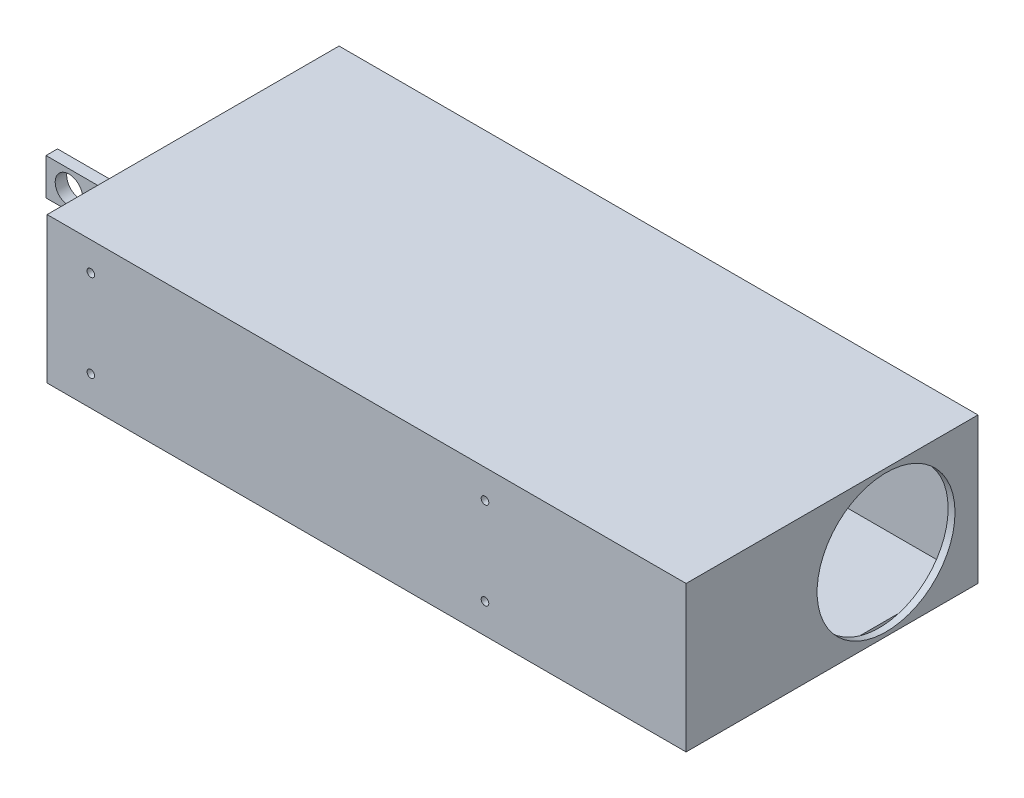
SolidWorks part; units mm, degrees
material "6061-T6 (SS)"
ref_plane "Front Plane" through (0, 0, 0) normal (0, 0, 1) x (1, 0, 0)
ref_plane "Top Plane" through (0, 0, 0) normal (0, 1, 0) x (1, 0, 0)
ref_plane "Right Plane" through (0, 0, 0) normal (1, 0, 0) x (0, 0, -1)
sketch "Sketch1" plane through (0, 0, 0) normal (0, 1, 0) x (1, 0, 0)
  line L1 (139, 63.5) -> (-139, 63.5)
  line L2 (139, 63.5) -> (139, -63.5)
  line L3 (139, -63.5) -> (-139, -63.5)
  line L4 (-139, 63.5) -> (-139, -63.5)
  line L5 (139, 63.5) -> (-139, -63.5) construction
  line L6 (139, -63.5) -> (-139, 63.5) construction
  point P0 (0, 0)
  dimension "D1" = 278
  dimension "D2" = 127
extrude "Boss-Extrude1" add sketch "Sketch1" along normal blind 63.5
sketch "Sketch7" plane through (139, 0, 0) normal (1, 0, 0) x (0, 0, -1)
  line L0 (23.5, 63.5) -> (23.5, 31.75) construction
  line L1 (-63.5, 63.5) -> (63.5, 63.5) construction
  line L2 (23.5, 31.75) -> (23.5, 0) construction
  line L3 (-63.5, 0) -> (63.5, 0) construction
  line L4 (63.5, 63.5) -> (63.5, 0) construction
  circle A0 centre (23.5, 31.75) radius 30
  dimension "D1" = 60
  dimension "D2" = 40
extrude "Cut-Extrude1" cut sketch "Sketch7" against normal blind 3
shell "Shell1" thickness 3 removed face at (136, 31.75, -53.5)
hole_wizard "M4x0.7 Tapped Hole1" positions "Sketch2" profile "Sketch3" tap size "M4x0.7" standard "ANSI Metric"
sketch "Sketch2" plane through (0, 0, 0) normal (0, -1, 0) x (-1, 0, 0)
  line L1 (-51.5, 51.25) -> (120, 51.25)
  line L2 (-51.5, 51.25) -> (-51.5, -50.25)
  line L3 (-51.5, -50.25) -> (120, -50.25)
  line L4 (120, 51.25) -> (120, -50.25)
  line L5 (-51.5, 51.25) -> (120, -50.25) construction
  line L6 (-51.5, -50.25) -> (120, 51.25) construction
  line L7 (139, 63.5) -> (139, -63.5) construction
  line L10 (-139, 63.5) -> (139, 63.5) construction
  point P2 (120, -50.25)
  point P89 (-51.5, 51.25)
  point P90 (-51.5, -50.25)
  point P91 (120, 51.25)
  dimension "D1" = 101.5
  dimension "D2" = 171.5
  dimension "D3" = 19
  dimension "D4" = 12.25
sketch "Sketch3" plane through (-120, 0, 50.25) normal (1, 0, 0) x (0, 0, -1)
  line L0 (0, 0) -> (0, 11.0914)
  line L1 (0, 11.0914) -> (1.65, 10.1)
  line L2 (1.65, 10.1) -> (1.65, 0)
  line L5 (1.65, 0) -> (0, 0)
  line L10 (0, 11.0914) -> (-1.65, 10.1) construction
  line L11 (0, -6.35) -> (0, 107.95) construction
  dimension "Tap Drill Dia." = 3.3
  dimension "Tap Drill Depth" = 10.1
  dimension "Drill Angle" = 118
cosmetic thread "Hole Thread1" parameters "D1"=8, "D2"=4
cosmetic thread "Hole Thread2" parameters "D1"=8, "D2"=4
cosmetic thread "Hole Thread3" parameters "D1"=8, "D2"=4
cosmetic thread "Hole Thread4" parameters "D1"=8, "D2"=4
hole_wizard "M4x0.7 Tapped Hole2" positions "Sketch4" profile "Sketch5" tap size "M4x0.7" standard "ANSI Metric"
sketch "Sketch4" plane through (0, 0, -63.5) normal (0, 0, -1) x (-1, 0, 0)
  line L1 (-51.5, 51) -> (120, 51)
  line L2 (-51.5, 51) -> (-51.5, 13)
  line L3 (-51.5, 13) -> (120, 13)
  line L4 (120, 51) -> (120, 13)
  line L5 (-51.5, 51) -> (120, 13) construction
  line L6 (-51.5, 13) -> (120, 51) construction
  line L8 (-139, 63.5) -> (139, 63.5) construction
  line L15 (139, 63.5) -> (139, 0) construction
  point P2 (120, 13)
  point P101 (-51.5, 51)
  point P102 (-51.5, 13)
  point P103 (120, 51)
  dimension "D1" = 171.5
  dimension "D2" = 38
  dimension "D3" = 19
  dimension "D4" = 12.5
sketch "Sketch5" plane through (-120, 13, -63.5) normal (1, 0, 0) x (0, 1, 0)
  line L0 (0, 0) -> (0, 11.0914)
  line L1 (0, 11.0914) -> (1.65, 10.1)
  line L2 (1.65, 10.1) -> (1.65, 0)
  line L5 (1.65, 0) -> (0, 0)
  line L10 (0, 11.0914) -> (-1.65, 10.1) construction
  line L11 (0, -6.35) -> (0, 107.95) construction
  dimension "Tap Drill Dia." = 3.3
  dimension "Tap Drill Depth" = 10.1
  dimension "Drill Angle" = 118
cosmetic thread "Hole Thread5" parameters "D1"=8, "D2"=4
cosmetic thread "Hole Thread6" parameters "D1"=8, "D2"=4
cosmetic thread "Hole Thread7" parameters "D1"=8, "D2"=4
cosmetic thread "Hole Thread8" parameters "D1"=8, "D2"=4
mirror "Mirror1" about plane through (0, 0, 0) normal (0, 0, 1) of "M4x0.7 Tapped Hole2"
sketch "Sketch6" plane through (-139, 0, 0) normal (-1, 0, 0) x (0, 0, 1)
  line L0 (-63.5, 0) -> (63.5, 0) construction
  line L1 (-5, 5) -> (0, 5)
  line L2 (-5, 5) -> (-5, 21)
  line L3 (-5, 21) -> (0, 21)
  line L4 (0, 5) -> (0, 21)
  line L5 (-5, 5) -> (0, 21) construction
  line L6 (-5, 21) -> (0, 5) construction
  line L7 (20, 31) -> (25, 31)
  line L8 (20, 31) -> (20, 47)
  line L9 (20, 47) -> (25, 47)
  line L10 (25, 31) -> (25, 47)
  line L11 (20, 31) -> (25, 47) construction
  line L12 (20, 47) -> (25, 31) construction
  point P0 (-2.5, 13)
  point P5 (22.5, 39)
  point P10 (0, 0)
  point P14 (0, 21.5279)
  point P17 (0, 0)
  dimension "D1" = 16
  dimension "D2" = 5
  dimension "D3" = 5
  dimension "D4" = 10
  dimension "D5" = 20
extrude "Boss-Extrude2" add sketch "Sketch6" along normal blind 39
sketch "Sketch8" plane through (0, 0, -5) normal (0, 0, -1) x (-1, 0, 0)
  line L0 (178, 21) -> (178, 5) construction
  line L1 (178, 13) -> (168, 13) construction
  line L2 (168, 39) -> (178, 39) construction
  line L3 (178, 47) -> (178, 31) construction
  circle A0 centre (168, 13) radius 6
  circle A1 centre (168, 39) radius 6
  point P7 (0, 0)
  dimension "D1" = 12
  dimension "D2" = 10
extrude "Cut-Extrude2" cut sketch "Sketch8" against normal through all
sketch "Sketch9" plane through (-139, 0, 0) normal (-1, 0, 0) x (0, 0, 1)
  line L0 (-63.5, 63.5) -> (-63.5, 0) construction
  line L1 (-55.5, 3) -> (-47.5, 3)
  line L2 (-55.5, 3) -> (-55.5, 8)
  line L3 (-55.5, 8) -> (-47.5, 8)
  line L4 (-47.5, 3) -> (-47.5, 8)
  line L5 (-63.5, 0) -> (63.5, 0) construction
  line L6 (-45.2, 3) -> (-37.2, 3)
  line L7 (-37.2, 3) -> (-37.2, 8)
  line L8 (-45.2, 8) -> (-37.2, 8)
  line L9 (-45.2, 3) -> (-45.2, 8)
  line L10 (-34.9, 3) -> (-26.9, 3)
  line L11 (-26.9, 3) -> (-26.9, 8)
  line L12 (-34.9, 8) -> (-26.9, 8)
  line L13 (-34.9, 3) -> (-34.9, 8)
  line L14 (-24.6, 3) -> (-16.6, 3)
  line L15 (-16.6, 3) -> (-16.6, 8)
  line L16 (-24.6, 8) -> (-16.6, 8)
  line L17 (-24.6, 3) -> (-24.6, 8)
  line L18 (-14.3, 3) -> (-6.3, 3) [skipped]
  line L19 (-6.3, 3) -> (-6.3, 8) [skipped]
  line L20 (-14.3, 8) -> (-6.3, 8) [skipped]
  line L21 (-14.3, 3) -> (-14.3, 8) [skipped]
  line L22 (-4, 3) -> (4, 3) [skipped]
  line L23 (4, 3) -> (4, 8) [skipped]
  line L24 (-4, 8) -> (4, 8) [skipped]
  line L25 (-4, 3) -> (-4, 8) [skipped]
  line L26 (6.3, 3) -> (14.3, 3)
  line L27 (14.3, 3) -> (14.3, 8)
  line L28 (6.3, 8) -> (14.3, 8)
  line L29 (6.3, 3) -> (6.3, 8)
  line L30 (16.6, 3) -> (24.6, 3)
  line L31 (24.6, 3) -> (24.6, 8)
  line L32 (16.6, 8) -> (24.6, 8)
  line L33 (16.6, 3) -> (16.6, 8)
  line L34 (26.9, 3) -> (34.9, 3)
  line L35 (34.9, 3) -> (34.9, 8)
  line L36 (26.9, 8) -> (34.9, 8)
  line L37 (26.9, 3) -> (26.9, 8)
  line L38 (37.2, 3) -> (45.2, 3)
  line L39 (45.2, 3) -> (45.2, 8)
  line L40 (37.2, 8) -> (45.2, 8)
  line L41 (37.2, 3) -> (37.2, 8)
  line L42 (47.5, 3) -> (55.5, 3)
  line L43 (55.5, 3) -> (55.5, 8)
  line L44 (47.5, 8) -> (55.5, 8)
  line L45 (47.5, 3) -> (47.5, 8)
  line L46 (-50.35, 15.3) -> (-42.35, 15.3)
  line L47 (-60.65, 15.3) -> (-52.65, 15.3)
  line L48 (-60.65, 15.3) -> (-60.65, 10.3)
  line L49 (-60.65, 10.3) -> (-52.65, 10.3)
  line L50 (-52.65, 15.3) -> (-52.65, 10.3)
  line L51 (-50.35, 10.3) -> (-42.35, 10.3)
  line L52 (-42.35, 15.3) -> (-42.35, 10.3)
  line L53 (-50.35, 15.3) -> (-50.35, 10.3)
  line L54 (-40.05, 15.3) -> (-32.05, 15.3)
  line L55 (-40.05, 10.3) -> (-32.05, 10.3)
  line L56 (-32.05, 15.3) -> (-32.05, 10.3)
  line L57 (-40.05, 15.3) -> (-40.05, 10.3)
  line L58 (-29.75, 15.3) -> (-21.75, 15.3)
  line L59 (-29.75, 10.3) -> (-21.75, 10.3)
  line L60 (-21.75, 15.3) -> (-21.75, 10.3)
  line L61 (-29.75, 15.3) -> (-29.75, 10.3)
  line L62 (-19.45, 15.3) -> (-11.45, 15.3)
  line L63 (-19.45, 10.3) -> (-11.45, 10.3)
  line L64 (-11.45, 15.3) -> (-11.45, 10.3)
  line L65 (-19.45, 15.3) -> (-19.45, 10.3)
  line L66 (-45.2, 17.6) -> (-37.2, 17.6)
  line L67 (-55.5, 22.6) -> (-47.5, 22.6)
  line L68 (-55.5, 22.6) -> (-55.5, 17.6)
  line L69 (-55.5, 17.6) -> (-47.5, 17.6)
  line L70 (1.15, 15.3) -> (9.15, 15.3)
  line L71 (1.15, 10.3) -> (9.15, 10.3)
  line L72 (9.15, 15.3) -> (9.15, 10.3)
  line L73 (1.15, 15.3) -> (1.15, 10.3)
  line L74 (11.45, 15.3) -> (19.45, 15.3)
  line L75 (11.45, 10.3) -> (19.45, 10.3)
  line L76 (19.45, 15.3) -> (19.45, 10.3)
  line L77 (11.45, 15.3) -> (11.45, 10.3)
  line L78 (21.75, 15.3) -> (29.75, 15.3)
  line L79 (21.75, 10.3) -> (29.75, 10.3)
  line L80 (29.75, 15.3) -> (29.75, 10.3)
  line L81 (21.75, 15.3) -> (21.75, 10.3)
  line L82 (32.05, 15.3) -> (40.05, 15.3)
  line L83 (32.05, 10.3) -> (40.05, 10.3)
  line L84 (40.05, 15.3) -> (40.05, 10.3)
  line L85 (32.05, 15.3) -> (32.05, 10.3)
  line L86 (42.35, 15.3) -> (50.35, 15.3)
  line L87 (42.35, 10.3) -> (50.35, 10.3)
  line L88 (50.35, 15.3) -> (50.35, 10.3)
  line L89 (42.35, 15.3) -> (42.35, 10.3)
  line L90 (52.65, 15.3) -> (60.65, 15.3)
  line L91 (52.65, 10.3) -> (60.65, 10.3)
  line L92 (60.65, 15.3) -> (60.65, 10.3)
  line L93 (52.65, 15.3) -> (52.65, 10.3)
  line L94 (63.5, 63.5) -> (63.5, 0) construction
  line L95 (-9.15, 15.3) -> (-1.15, 15.3) [skipped]
  line L96 (-9.15, 10.3) -> (-1.15, 10.3) [skipped]
  line L97 (-1.15, 15.3) -> (-1.15, 10.3) [skipped]
  line L98 (-9.15, 15.3) -> (-9.15, 10.3) [skipped]
  line L99 (-47.5, 22.6) -> (-47.5, 17.6)
  line L100 (-60.65, 29.9) -> (-52.65, 29.9)
  line L101 (-60.65, 29.9) -> (-60.65, 24.9)
  line L102 (-60.65, 24.9) -> (-52.65, 24.9)
  line L103 (-52.65, 29.9) -> (-52.65, 24.9)
  line L104 (-55.5, 37.2) -> (-47.5, 37.2)
  line L105 (-55.5, 37.2) -> (-55.5, 32.2)
  line L106 (-55.5, 32.2) -> (-47.5, 32.2)
  line L107 (-47.5, 37.2) -> (-47.5, 32.2)
  line L108 (-60.65, 44.5) -> (-52.65, 44.5)
  line L109 (-60.65, 44.5) -> (-60.65, 39.5)
  line L110 (-60.65, 39.5) -> (-52.65, 39.5)
  line L111 (-52.65, 44.5) -> (-52.65, 39.5)
  line L112 (-55.5, 51.8) -> (-47.5, 51.8)
  line L113 (-55.5, 51.8) -> (-55.5, 46.8)
  line L114 (-55.5, 46.8) -> (-47.5, 46.8)
  line L115 (-47.5, 51.8) -> (-47.5, 46.8)
  line L116 (-60.65, 59.1) -> (-52.65, 59.1)
  line L117 (-60.65, 59.1) -> (-60.65, 54.1)
  line L118 (-60.65, 54.1) -> (-52.65, 54.1)
  line L119 (-52.65, 59.1) -> (-52.65, 54.1)
  line L120 (-37.2, 22.6) -> (-37.2, 17.6)
  line L121 (-45.2, 22.6) -> (-37.2, 22.6)
  line L122 (-45.2, 22.6) -> (-45.2, 17.6)
  line L123 (-34.9, 17.6) -> (-26.9, 17.6)
  line L124 (-26.9, 22.6) -> (-26.9, 17.6)
  line L125 (-34.9, 22.6) -> (-26.9, 22.6)
  line L126 (-34.9, 22.6) -> (-34.9, 17.6)
  line L127 (-24.6, 17.6) -> (-16.6, 17.6)
  line L128 (-16.6, 22.6) -> (-16.6, 17.6)
  line L129 (-24.6, 22.6) -> (-16.6, 22.6)
  line L130 (-24.6, 22.6) -> (-24.6, 17.6)
  line L131 (-14.3, 17.6) -> (-6.3, 17.6) [skipped]
  line L132 (-6.3, 22.6) -> (-6.3, 17.6) [skipped]
  line L133 (-14.3, 22.6) -> (-6.3, 22.6) [skipped]
  line L134 (-14.3, 22.6) -> (-14.3, 17.6) [skipped]
  line L135 (-4, 17.6) -> (4, 17.6) [skipped]
  line L136 (4, 22.6) -> (4, 17.6) [skipped]
  line L137 (-4, 22.6) -> (4, 22.6) [skipped]
  line L138 (-4, 22.6) -> (-4, 17.6) [skipped]
  line L139 (6.3, 17.6) -> (14.3, 17.6)
  line L140 (14.3, 22.6) -> (14.3, 17.6)
  line L141 (6.3, 22.6) -> (14.3, 22.6)
  line L142 (6.3, 22.6) -> (6.3, 17.6)
  line L143 (16.6, 17.6) -> (24.6, 17.6)
  line L144 (24.6, 22.6) -> (24.6, 17.6)
  line L145 (16.6, 22.6) -> (24.6, 22.6)
  line L146 (16.6, 22.6) -> (16.6, 17.6)
  line L147 (26.9, 17.6) -> (34.9, 17.6)
  line L148 (34.9, 22.6) -> (34.9, 17.6)
  line L149 (26.9, 22.6) -> (34.9, 22.6)
  line L150 (26.9, 22.6) -> (26.9, 17.6)
  line L151 (37.2, 17.6) -> (45.2, 17.6)
  line L152 (45.2, 22.6) -> (45.2, 17.6)
  line L153 (37.2, 22.6) -> (45.2, 22.6)
  line L154 (37.2, 22.6) -> (37.2, 17.6)
  line L155 (47.5, 17.6) -> (55.5, 17.6)
  line L156 (55.5, 22.6) -> (55.5, 17.6)
  line L157 (47.5, 22.6) -> (55.5, 22.6)
  line L158 (47.5, 22.6) -> (47.5, 17.6)
  line L159 (-50.35, 29.9) -> (-42.35, 29.9)
  line L160 (-50.35, 29.9) -> (-50.35, 24.9)
  line L161 (-50.35, 24.9) -> (-42.35, 24.9)
  line L162 (-42.35, 29.9) -> (-42.35, 24.9)
  line L163 (-40.05, 29.9) -> (-32.05, 29.9)
  line L164 (-40.05, 29.9) -> (-40.05, 24.9)
  line L165 (-40.05, 24.9) -> (-32.05, 24.9)
  line L166 (-32.05, 29.9) -> (-32.05, 24.9)
  line L167 (-29.75, 29.9) -> (-21.75, 29.9)
  line L168 (-29.75, 29.9) -> (-29.75, 24.9)
  line L169 (-29.75, 24.9) -> (-21.75, 24.9)
  line L170 (-21.75, 29.9) -> (-21.75, 24.9)
  line L171 (-19.45, 29.9) -> (-11.45, 29.9)
  line L172 (-19.45, 29.9) -> (-19.45, 24.9)
  line L173 (-19.45, 24.9) -> (-11.45, 24.9)
  line L174 (-11.45, 29.9) -> (-11.45, 24.9)
  line L175 (-9.15, 29.9) -> (-1.15, 29.9)
  line L176 (-9.15, 29.9) -> (-9.15, 24.9)
  line L177 (-9.15, 24.9) -> (-1.15, 24.9)
  line L178 (-1.15, 29.9) -> (-1.15, 24.9)
  line L179 (1.15, 29.9) -> (9.15, 29.9)
  line L180 (1.15, 29.9) -> (1.15, 24.9)
  line L181 (1.15, 24.9) -> (9.15, 24.9)
  line L182 (9.15, 29.9) -> (9.15, 24.9)
  line L183 (11.45, 29.9) -> (19.45, 29.9)
  line L184 (11.45, 29.9) -> (11.45, 24.9)
  line L185 (11.45, 24.9) -> (19.45, 24.9)
  line L186 (19.45, 29.9) -> (19.45, 24.9)
  line L187 (21.75, 29.9) -> (29.75, 29.9)
  line L188 (21.75, 29.9) -> (21.75, 24.9)
  line L189 (21.75, 24.9) -> (29.75, 24.9)
  line L190 (29.75, 29.9) -> (29.75, 24.9)
  line L191 (32.05, 29.9) -> (40.05, 29.9)
  line L192 (32.05, 29.9) -> (32.05, 24.9)
  line L193 (32.05, 24.9) -> (40.05, 24.9)
  line L194 (40.05, 29.9) -> (40.05, 24.9)
  line L195 (42.35, 29.9) -> (50.35, 29.9)
  line L196 (42.35, 29.9) -> (42.35, 24.9)
  line L197 (42.35, 24.9) -> (50.35, 24.9)
  line L198 (50.35, 29.9) -> (50.35, 24.9)
  line L199 (52.65, 29.9) -> (60.65, 29.9)
  line L200 (52.65, 29.9) -> (52.65, 24.9)
  line L201 (52.65, 24.9) -> (60.65, 24.9)
  line L202 (60.65, 29.9) -> (60.65, 24.9)
  line L203 (-45.2, 37.2) -> (-37.2, 37.2)
  line L204 (-45.2, 37.2) -> (-45.2, 32.2)
  line L205 (-45.2, 32.2) -> (-37.2, 32.2)
  line L206 (-37.2, 37.2) -> (-37.2, 32.2)
  line L207 (-34.9, 37.2) -> (-26.9, 37.2)
  line L208 (-34.9, 37.2) -> (-34.9, 32.2)
  line L209 (-34.9, 32.2) -> (-26.9, 32.2)
  line L210 (-26.9, 37.2) -> (-26.9, 32.2)
  line L211 (-24.6, 37.2) -> (-16.6, 37.2)
  line L212 (-24.6, 37.2) -> (-24.6, 32.2)
  line L213 (-24.6, 32.2) -> (-16.6, 32.2)
  line L214 (-16.6, 37.2) -> (-16.6, 32.2)
  line L215 (-14.3, 37.2) -> (-6.3, 37.2)
  line L216 (-14.3, 37.2) -> (-14.3, 32.2)
  line L217 (-14.3, 32.2) -> (-6.3, 32.2)
  line L218 (-6.3, 37.2) -> (-6.3, 32.2)
  line L219 (-4, 37.2) -> (4, 37.2)
  line L220 (-4, 37.2) -> (-4, 32.2)
  line L221 (-4, 32.2) -> (4, 32.2)
  line L222 (4, 37.2) -> (4, 32.2)
  line L223 (6.3, 37.2) -> (14.3, 37.2) [skipped]
  line L224 (6.3, 37.2) -> (6.3, 32.2) [skipped]
  line L225 (6.3, 32.2) -> (14.3, 32.2) [skipped]
  line L226 (14.3, 37.2) -> (14.3, 32.2) [skipped]
  line L227 (16.6, 37.2) -> (24.6, 37.2) [skipped]
  line L228 (16.6, 37.2) -> (16.6, 32.2) [skipped]
  line L229 (16.6, 32.2) -> (24.6, 32.2) [skipped]
  line L230 (24.6, 37.2) -> (24.6, 32.2) [skipped]
  line L231 (26.9, 37.2) -> (34.9, 37.2)
  line L232 (26.9, 37.2) -> (26.9, 32.2)
  line L233 (26.9, 32.2) -> (34.9, 32.2)
  line L234 (34.9, 37.2) -> (34.9, 32.2)
  line L235 (37.2, 37.2) -> (45.2, 37.2)
  line L236 (37.2, 37.2) -> (37.2, 32.2)
  line L237 (37.2, 32.2) -> (45.2, 32.2)
  line L238 (45.2, 37.2) -> (45.2, 32.2)
  line L239 (47.5, 37.2) -> (55.5, 37.2)
  line L240 (47.5, 37.2) -> (47.5, 32.2)
  line L241 (47.5, 32.2) -> (55.5, 32.2)
  line L242 (55.5, 37.2) -> (55.5, 32.2)
  line L243 (-50.35, 44.5) -> (-42.35, 44.5)
  line L244 (-50.35, 44.5) -> (-50.35, 39.5)
  line L245 (-50.35, 39.5) -> (-42.35, 39.5)
  line L246 (-42.35, 44.5) -> (-42.35, 39.5)
  line L247 (-40.05, 44.5) -> (-32.05, 44.5)
  line L248 (-40.05, 44.5) -> (-40.05, 39.5)
  line L249 (-40.05, 39.5) -> (-32.05, 39.5)
  line L250 (-32.05, 44.5) -> (-32.05, 39.5)
  line L251 (-29.75, 44.5) -> (-21.75, 44.5)
  line L252 (-29.75, 44.5) -> (-29.75, 39.5)
  line L253 (-29.75, 39.5) -> (-21.75, 39.5)
  line L254 (-21.75, 44.5) -> (-21.75, 39.5)
  line L255 (-19.45, 44.5) -> (-11.45, 44.5)
  line L256 (-19.45, 44.5) -> (-19.45, 39.5)
  line L257 (-19.45, 39.5) -> (-11.45, 39.5)
  line L258 (-11.45, 44.5) -> (-11.45, 39.5)
  line L259 (-9.15, 44.5) -> (-1.15, 44.5)
  line L260 (-9.15, 44.5) -> (-9.15, 39.5)
  line L261 (-9.15, 39.5) -> (-1.15, 39.5)
  line L262 (-1.15, 44.5) -> (-1.15, 39.5)
  line L263 (1.15, 44.5) -> (9.15, 44.5)
  line L264 (1.15, 44.5) -> (1.15, 39.5)
  line L265 (1.15, 39.5) -> (9.15, 39.5)
  line L266 (9.15, 44.5) -> (9.15, 39.5)
  line L267 (11.45, 44.5) -> (19.45, 44.5) [skipped]
  line L268 (11.45, 44.5) -> (11.45, 39.5) [skipped]
  line L269 (11.45, 39.5) -> (19.45, 39.5) [skipped]
  line L270 (19.45, 44.5) -> (19.45, 39.5) [skipped]
  line L271 (21.75, 44.5) -> (29.75, 44.5) [skipped]
  line L272 (21.75, 44.5) -> (21.75, 39.5) [skipped]
  line L273 (21.75, 39.5) -> (29.75, 39.5) [skipped]
  line L274 (29.75, 44.5) -> (29.75, 39.5) [skipped]
  line L275 (32.05, 44.5) -> (40.05, 44.5)
  line L276 (32.05, 44.5) -> (32.05, 39.5)
  line L277 (32.05, 39.5) -> (40.05, 39.5)
  line L278 (40.05, 44.5) -> (40.05, 39.5)
  line L279 (42.35, 44.5) -> (50.35, 44.5)
  line L280 (42.35, 44.5) -> (42.35, 39.5)
  line L281 (42.35, 39.5) -> (50.35, 39.5)
  line L282 (50.35, 44.5) -> (50.35, 39.5)
  line L283 (52.65, 44.5) -> (60.65, 44.5)
  line L284 (52.65, 44.5) -> (52.65, 39.5)
  line L285 (52.65, 39.5) -> (60.65, 39.5)
  line L286 (60.65, 44.5) -> (60.65, 39.5)
  line L287 (-45.2, 51.8) -> (-37.2, 51.8)
  line L288 (-45.2, 51.8) -> (-45.2, 46.8)
  line L289 (-45.2, 46.8) -> (-37.2, 46.8)
  line L290 (-37.2, 51.8) -> (-37.2, 46.8)
  line L291 (-34.9, 51.8) -> (-26.9, 51.8) [skipped]
  line L292 (-34.9, 51.8) -> (-34.9, 46.8) [skipped]
  line L293 (-34.9, 46.8) -> (-26.9, 46.8) [skipped]
  line L294 (-26.9, 51.8) -> (-26.9, 46.8) [skipped]
  line L295 (-24.6, 51.8) -> (-16.6, 51.8)
  line L296 (-24.6, 51.8) -> (-24.6, 46.8)
  line L297 (-24.6, 46.8) -> (-16.6, 46.8)
  line L298 (-16.6, 51.8) -> (-16.6, 46.8)
  line L299 (-14.3, 51.8) -> (-6.3, 51.8)
  line L300 (-14.3, 51.8) -> (-14.3, 46.8)
  line L301 (-14.3, 46.8) -> (-6.3, 46.8)
  line L302 (-6.3, 51.8) -> (-6.3, 46.8)
  line L303 (-4, 51.8) -> (4, 51.8)
  line L304 (-4, 51.8) -> (-4, 46.8)
  line L305 (-4, 46.8) -> (4, 46.8)
  line L306 (4, 51.8) -> (4, 46.8)
  line L307 (6.3, 51.8) -> (14.3, 51.8)
  line L308 (6.3, 51.8) -> (6.3, 46.8)
  line L309 (6.3, 46.8) -> (14.3, 46.8)
  line L310 (14.3, 51.8) -> (14.3, 46.8)
  line L311 (16.6, 51.8) -> (24.6, 51.8) [skipped]
  line L312 (16.6, 51.8) -> (16.6, 46.8) [skipped]
  line L313 (16.6, 46.8) -> (24.6, 46.8) [skipped]
  line L314 (24.6, 51.8) -> (24.6, 46.8) [skipped]
  line L315 (26.9, 51.8) -> (34.9, 51.8) [skipped]
  line L316 (26.9, 51.8) -> (26.9, 46.8) [skipped]
  line L317 (26.9, 46.8) -> (34.9, 46.8) [skipped]
  line L318 (34.9, 51.8) -> (34.9, 46.8) [skipped]
  line L319 (37.2, 51.8) -> (45.2, 51.8) [skipped]
  line L320 (37.2, 51.8) -> (37.2, 46.8) [skipped]
  line L321 (37.2, 46.8) -> (45.2, 46.8) [skipped]
  line L322 (45.2, 51.8) -> (45.2, 46.8) [skipped]
  line L323 (47.5, 51.8) -> (55.5, 51.8) [skipped]
  line L324 (47.5, 51.8) -> (47.5, 46.8) [skipped]
  line L325 (47.5, 46.8) -> (55.5, 46.8) [skipped]
  line L326 (55.5, 51.8) -> (55.5, 46.8) [skipped]
  line L327 (-50.35, 59.1) -> (-42.35, 59.1)
  line L328 (-50.35, 59.1) -> (-50.35, 54.1)
  line L329 (-50.35, 54.1) -> (-42.35, 54.1)
  line L330 (-42.35, 59.1) -> (-42.35, 54.1)
  line L331 (-40.05, 59.1) -> (-32.05, 59.1) [skipped]
  line L332 (-40.05, 59.1) -> (-40.05, 54.1) [skipped]
  line L333 (-40.05, 54.1) -> (-32.05, 54.1) [skipped]
  line L334 (-32.05, 59.1) -> (-32.05, 54.1) [skipped]
  line L335 (-29.75, 59.1) -> (-21.75, 59.1) [skipped]
  line L336 (-29.75, 59.1) -> (-29.75, 54.1) [skipped]
  line L337 (-29.75, 54.1) -> (-21.75, 54.1) [skipped]
  line L338 (-21.75, 59.1) -> (-21.75, 54.1) [skipped]
  line L339 (-19.45, 59.1) -> (-11.45, 59.1)
  line L340 (-19.45, 59.1) -> (-19.45, 54.1)
  line L341 (-19.45, 54.1) -> (-11.45, 54.1)
  line L342 (-11.45, 59.1) -> (-11.45, 54.1)
  line L343 (-9.15, 59.1) -> (-1.15, 59.1)
  line L344 (-9.15, 59.1) -> (-9.15, 54.1)
  line L345 (-9.15, 54.1) -> (-1.15, 54.1)
  line L346 (-1.15, 59.1) -> (-1.15, 54.1)
  line L347 (1.15, 59.1) -> (9.15, 59.1)
  line L348 (1.15, 59.1) -> (1.15, 54.1)
  line L349 (1.15, 54.1) -> (9.15, 54.1)
  line L350 (9.15, 59.1) -> (9.15, 54.1)
  line L351 (11.45, 59.1) -> (19.45, 59.1) [skipped]
  line L352 (11.45, 59.1) -> (11.45, 54.1) [skipped]
  line L353 (11.45, 54.1) -> (19.45, 54.1) [skipped]
  line L354 (19.45, 59.1) -> (19.45, 54.1) [skipped]
  line L355 (21.75, 59.1) -> (29.75, 59.1) [skipped]
  line L356 (21.75, 59.1) -> (21.75, 54.1) [skipped]
  line L357 (21.75, 54.1) -> (29.75, 54.1) [skipped]
  line L358 (29.75, 59.1) -> (29.75, 54.1) [skipped]
  line L359 (32.05, 59.1) -> (40.05, 59.1) [skipped]
  line L360 (32.05, 59.1) -> (32.05, 54.1) [skipped]
  line L361 (32.05, 54.1) -> (40.05, 54.1) [skipped]
  line L362 (40.05, 59.1) -> (40.05, 54.1) [skipped]
  line L363 (42.35, 59.1) -> (50.35, 59.1) [skipped]
  line L364 (42.35, 59.1) -> (42.35, 54.1) [skipped]
  line L365 (42.35, 54.1) -> (50.35, 54.1) [skipped]
  line L366 (50.35, 59.1) -> (50.35, 54.1) [skipped]
  line L367 (52.65, 59.1) -> (60.65, 59.1) [skipped]
  line L368 (52.65, 59.1) -> (52.65, 54.1) [skipped]
  line L369 (52.65, 54.1) -> (60.65, 54.1) [skipped]
  line L370 (60.65, 59.1) -> (60.65, 54.1) [skipped]
  point P126 (-44.4795, 17.6)
  dimension "D1" = 8
  dimension "D2" = 5
  dimension "D3" = 8
  dimension "D4" = 3
  dimension "D6" = 10.3
  dimension "D7" = 5.15
  dimension "D8" = 2.3
  dimension "D9" = 2.3
  dimension "D11" = 2.85
  dimension "D12" = 2.85
  dimension "D13" = 8
  dimension "D14" = 2.3
  dimension "D15" = 2.3
  dimension "D16" = 2.3
  dimension "D17" = 2.3
  dimension "D18" = 2.3
  dimension "D19" = 2.3
  dimension "D5" = 11
  dimension "D10" = 12
  dimension "D20" = 11
  dimension "D22" = 12
  dimension "D24" = 11
  dimension "D26" = 12
  dimension "D27" = 11
  dimension "D28" = 12
extrude "Cut-Extrude3" cut sketch "Sketch9" against normal blind 4
equation "\"D7@Sketch9\" = ( \"D1@Sketch9\" / 2 ) + ( \"D8@Sketch9\" / 2 )"
equation "\"D9@Sketch9\"= \"D8@Sketch9\""
equation "\"D11@Sketch9\"= \"D12@Sketch9\""
equation "\"D13@Sketch9\"= \"D3@Sketch9\""
equation "\"D14@Sketch9\"=\"D8@Sketch9\""
equation "\"D15@Sketch9\"=\"D8@Sketch9\""
equation "\"D16@Sketch9\"=\"D8@Sketch9\""
equation "\"D17@Sketch9\"=\"D8@Sketch9\""
equation "\"D18@Sketch9\"=\"D8@Sketch9\""
equation "\"D19@Sketch9\"=\"D8@Sketch9\""
